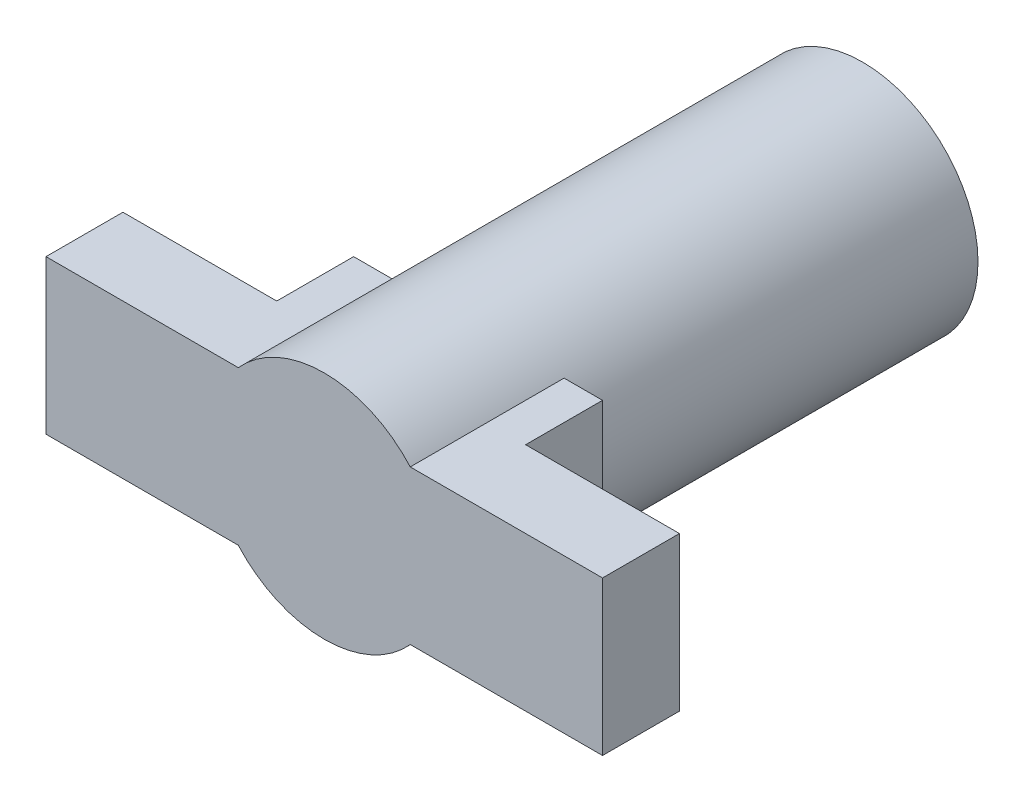
SolidWorks part; units mm, degrees
ref_plane "Alzado" through (0, 0, 0) normal (0, 0, 1) x (1, 0, 0)
ref_plane "Planta" through (0, 0, 0) normal (0, 1, 0) x (1, 0, 0)
ref_plane "Vista lateral" through (0, 0, 0) normal (1, 0, 0) x (0, 0, -1)
sketch "Croquis1" plane through (0, 0, 0) normal (0, 0, 1) x (1, 0, 0)
  circle A0 centre (0, 0) radius 15
  dimension "D1" = 30
extrude "Saliente-Extruir1" add sketch "Croquis1" along normal mid plane 70
sketch "Croquis10" plane through (0, 0, 35) normal (0, 0, 1) x (1, 0, 0)
  line L0 (11.1803, 0) -> (-11.1803, 0) construction
  line L1 (0, 0) -> (0, 10.6419) construction
  line L2 (-11.1803, -10) -> (-11.1803, 10)
  line L3 (-11.1803, 10) -> (-36.1803, 10)
  line L4 (-36.1803, 10) -> (-36.1803, -10)
  line L5 (-36.1803, -10) -> (-11.1803, -10)
  line L6 (36.1803, 10) -> (36.1803, -10)
  line L7 (11.1803, 10) -> (36.1803, 10)
  line L8 (11.1803, -10) -> (11.1803, 10)
  line L9 (36.1803, -10) -> (11.1803, -10)
  circle A0 centre (0, 0) radius 15 construction
  point P5 (0, 0)
  point P13 (-11.1803, 0)
  dimension "D1" = 25
  dimension "D2" = 20
extrude "Saliente-Extruir8" add sketch "Croquis10" against normal blind 20
sketch "Croquis11" plane through (0, 0, 15) normal (0, 0, 1) x (1, 0, 0)
  line L0 (-36.1803, 10) -> (-16.1803, 10)
  line L1 (-11.1803, 10) -> (-36.1803, 10) construction
  line L2 (-16.1803, 10) -> (-16.1803, -10)
  line L3 (-36.1803, -10) -> (-11.1803, -10) construction
  line L4 (-16.1803, -10) -> (-36.1803, -10)
  line L5 (-36.1803, -10) -> (-36.1803, 10)
  line L6 (0, 0) -> (0, 7.4469) construction
  line L7 (16.1803, -10) -> (36.1803, -10)
  line L8 (16.1803, 10) -> (16.1803, -10)
  line L9 (36.1803, 10) -> (16.1803, 10)
  line L10 (36.1803, -10) -> (36.1803, 10)
  dimension "D1" = 20
extrude "Cortar-Extruir1" cut sketch "Croquis11" along normal blind 10
